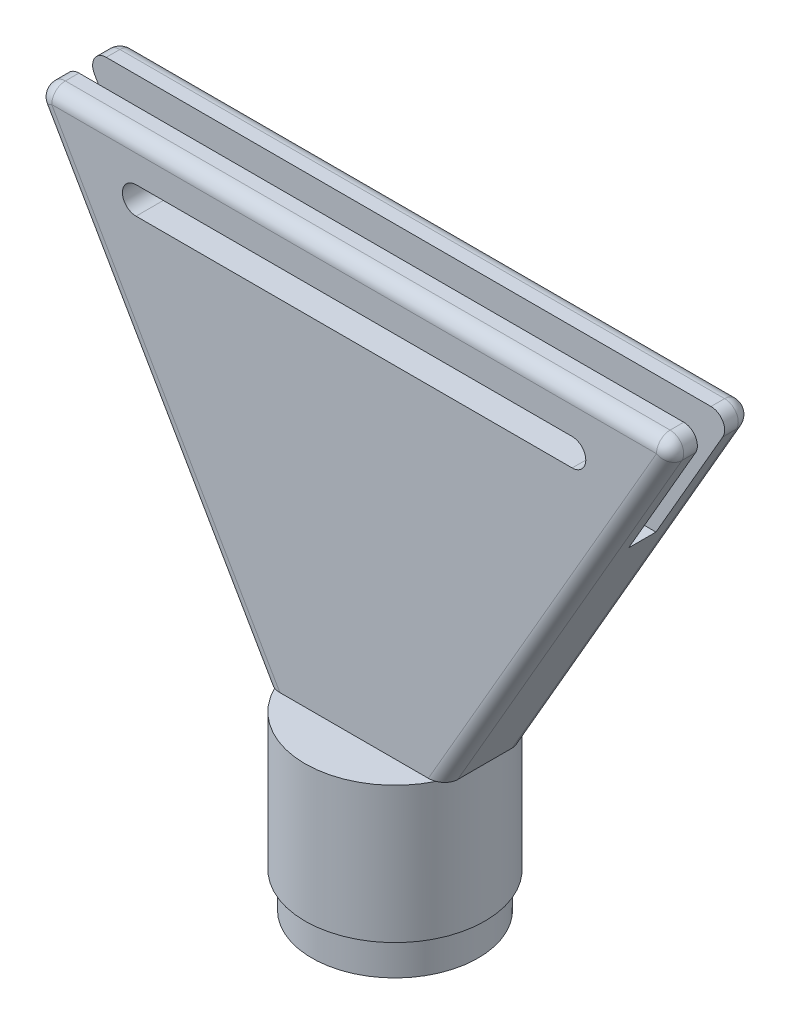
SolidWorks part; units mm, degrees
ref_plane "Front Plane" through (0, 0, 0) normal (0, 0, 1) x (1, 0, 0)
ref_plane "Top Plane" through (0, 0, 0) normal (0, 1, 0) x (1, 0, 0)
ref_plane "Right Plane" through (0, 0, 0) normal (1, 0, 0) x (0, 0, -1)
sketch "Sketch1" plane through (0, 0, 0) normal (0, 1, 0) x (1, 0, 0)
  circle A0 centre (0, 0) radius 15.494
  dimension "D1" = 30.988
extrude "Boss-Extrude1" add sketch "Sketch1" along normal blind 6.604
sketch "Sketch2" plane through (0, 6.604, 0) normal (0, 1, 0) x (1, 0, 0)
  circle A0 centre (0, 0) radius 16.764
  dimension "D1" = 33.528
extrude "Boss-Extrude2" add sketch "Sketch2" along normal blind 25.4
sketch "Sketch3" plane through (0, 32.004, 0) normal (0, 1, 0) x (1, 0, 0)
  circle A2 centre (0, 0) radius 16.764
  circle A3 centre (0, 0) radius 16.764
  dimension "D1" = 0
sketch "Sketch4" plane through (0, 0, 0) normal (0, 0, 1) x (1, 0, 0)
  line L0 (16.764, 32.004) -> (60.7581, 108.204)
  line L1 (60.7581, 108.204) -> (-60.7581, 108.204)
  line L2 (0, 108.204) -> (0, 32.004) construction
  line L3 (16.764, 32.004) -> (-16.764, 32.004) construction
  line L4 (-16.764, 32.004) -> (16.764, 32.004)
  line L5 (-16.764, 32.004) -> (-60.7581, 108.204)
  dimension "D1" = 120
  dimension "D2" = 76.2
extrude "Boss-Extrude3" add sketch "Sketch4" along normal mid plane 15.24
fillet "Fillet1" radius 2.54 8 edges at (60.7581, 108.204, 0) (-60.7581, 108.204, 0) (0, 108.204, 7.62) (0, 108.204, -7.62) (-38.761, 70.104, 7.62) (-38.761, 70.104, -7.62) (38.761, 70.104, 7.62) (38.761, 70.104, -7.62)
sketch "Sketch5" plane through (0, 108.204, 0) normal (0, 1, 0) x (1, 0, 0)
  line L0 (58.8987, -5.08) -> (58.8987, 5.08) construction
  line L1 (-58.8987, 2.54) -> (58.8987, 2.54)
  line L2 (-58.8987, 2.54) -> (-58.8987, -2.54)
  line L3 (-58.8987, -2.54) -> (58.8987, -2.54)
  line L4 (58.8987, 2.54) -> (58.8987, -2.54)
  line L5 (-58.8987, 2.54) -> (58.8987, -2.54) construction
  line L6 (-58.8987, -2.54) -> (58.8987, 2.54) construction
  point P0 (0, 0)
  dimension "D1" = 5.08
extrude "Cut-Extrude1" cut sketch "Sketch5" against normal blind 25.4
sketch "Sketch6" plane through (0, 0, -7.62) normal (0, 0, -1) x (-1, 0, 0)
  line L0 (-40.64, 98.044) -> (40.64, 98.044) construction
  line L1 (-40.64, 100.584) -> (40.64, 100.584)
  line L2 (-40.64, 95.504) -> (40.64, 95.504)
  line L3 (56.3587, 105.664) -> (-56.3587, 105.664) construction
  line L4 (0, 98.044) -> (0, 105.664) construction
  line L5 (-56.3587, 108.204) -> (56.3587, 108.204) construction
  arc A0 (-40.64, 100.584) -> (-40.64, 95.504) centre (-40.64, 98.044) ccw
  arc A1 (40.64, 95.504) -> (40.64, 100.584) centre (40.64, 98.044) ccw
  point P2 (0, 98.044)
  dimension "D1" = 81.28
  dimension "D2" = 10.16
  dimension "D3" = 5.08
extrude "Cut-Extrude2" cut sketch "Sketch6" against normal blind 25.4
